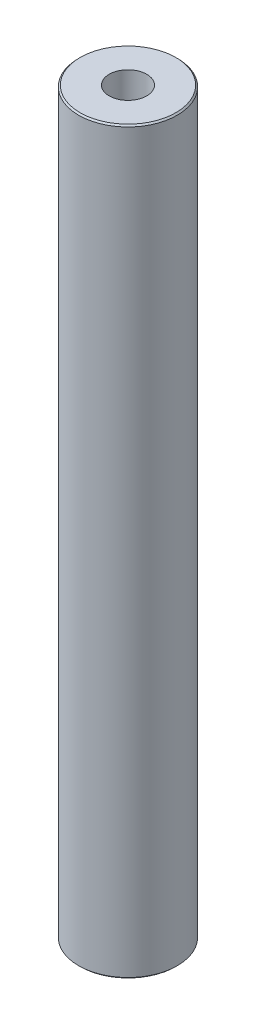
SolidWorks part; units mm, degrees
ref_plane "Front Plane" through (0, 0, 0) normal (0, 0, 1) x (1, 0, 0)
ref_plane "Top Plane" through (0, 0, 0) normal (0, 1, 0) x (1, 0, 0)
ref_plane "Right Plane" through (0, 0, 0) normal (1, 0, 0) x (0, 0, -1)
sketch "Sketch1" plane through (0, 0, 0) normal (0, 1, 0) x (1, 0, 0)
  circle A0 centre (0, 0) radius 40
  dimension "SHAFT_OD" = 80
extrude "Boss-Extrude1" add sketch "Sketch1" along normal blind 600
sketch "Sketch2" plane through (0, 0, 0) normal (0, 1, 0) x (1, 0, 0)
  circle A0 centre (0, 0) radius 15.2357
  dimension "BORE_D" = 30.4715
extrude "Cut-Extrude1" cut sketch "Sketch2" along normal through all
chamfer "Chamfer1" distance 1.1817 angle 44.416 2 edges at (0, 600, 40) (0, 0, 40) first distance on face at (0, 600, 40) first distance on face at (0, 0, 15.2357)
